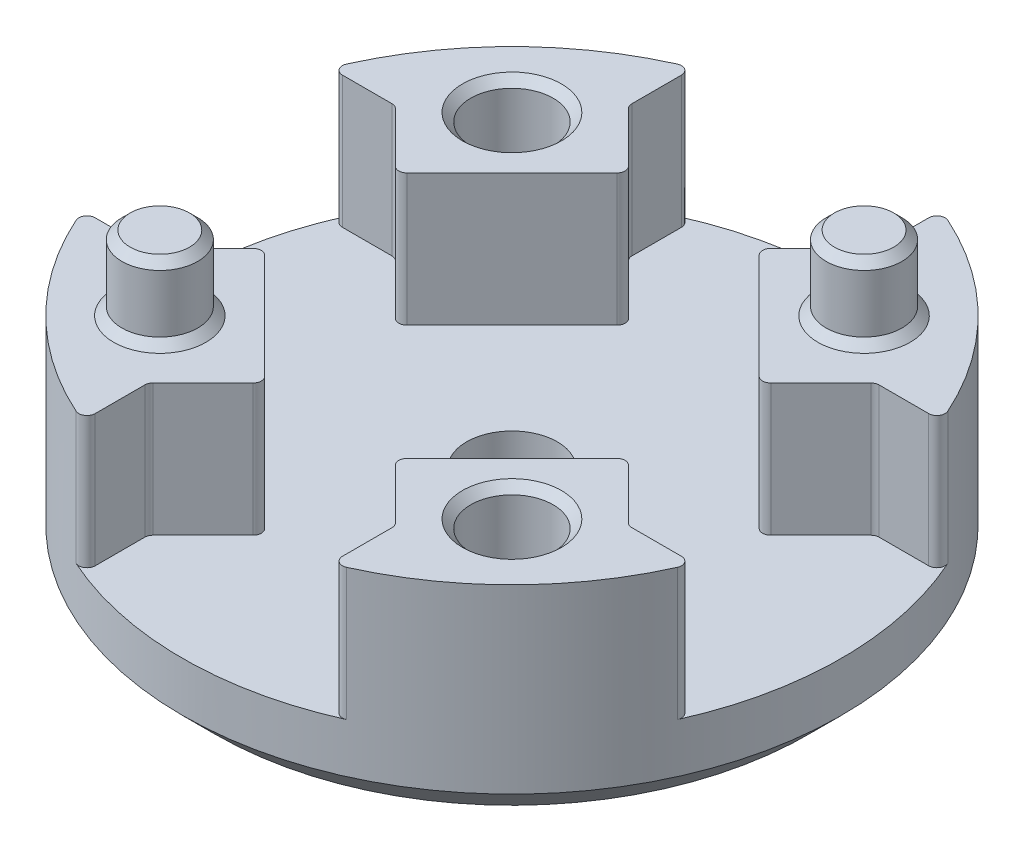
SolidWorks part; units mm, degrees
ref_plane "前视基准面" through (0, 0, 0) normal (0, 0, 1) x (1, 0, 0)
ref_plane "上视基准面" through (0, 0, 0) normal (0, 1, 0) x (1, 0, 0)
ref_plane "右视基准面" through (0, 0, 0) normal (1, 0, 0) x (0, 0, -1)
sketch "草图1" plane through (0, 0, 0) normal (0, 1, 0) x (1, 0, 0)
  circle A0 centre (0, 0) radius 20
  dimension "D1" = 40
extrude "凸台-拉伸1" add sketch "草图1" along normal blind 5
sketch "草图2" plane through (0, 5, 0) normal (0, 1, 0) x (1, 0, 0)
  line L0 (0, -15) -> (7.5, -7.5) construction
  line L1 (0, -15) -> (-7.5, -7.5) construction
  line L2 (7.5, -7.5) -> (0, 0) construction
  line L3 (-7.5, -7.5) -> (0, 0) construction
  line L4 (0, -15) -> (0, 0) construction
  line L5 (7.5, -7.5) -> (-7.5, -7.5) construction
  line L6 (14.5711, -7.5) -> (7.5, -14.5711) construction
  line L7 (14.5711, -7.5) -> (11.0355, -3.9645)
  line L8 (7.5, -14.5711) -> (3.9645, -11.0355)
  line L9 (11.0355, -3.9645) -> (3.9645, -11.0355)
  line L10 (14.5711, -7.5) -> (3.9645, -11.0355) construction
  line L11 (7.5, -14.5711) -> (11.0355, -3.9645) construction
  line L12 (7.5, -14.5711) -> (7.5, -18.5405)
  line L13 (14.5711, -7.5) -> (18.5405, -7.5)
  circle A0 centre (0, 0) radius 20 construction
  arc A1 (7.5, -18.5405) -> (18.5405, -7.5) centre (0, 0) ccw
  point P1 (0, -7.5)
  point P2 (9.2678, -9.2678)
  dimension "D1" = 15
  dimension "D2" = 5
  dimension "D3" = 5
extrude "凸台-拉伸2" add sketch "草图2" along normal blind 8
fillet "圆角1" radius 0.5 6 edges at (18.5405, 9, 7.5) (14.5711, 9, 7.5) (7.5, 9, 18.5405) (7.5, 9, 14.5711) (11.0355, 9, 3.9645) (3.9645, 9, 11.0355)
pattern_circular "阵列(圆周)1" count 4 over 360 about axis through (0, 5, 0) along (0, -1, 0) of "凸台-拉伸2", "圆角1" reverse direction yes
sketch "草图3" plane through (0, 13, 0) normal (0, 1, 0) x (1, 0, 0)
  line L0 (10.682, -10.682) -> (0, 0) construction
  line L1 (10.682, -4.318) -> (4.318, -10.682) construction
  line L2 (0, 0) -> (10.682, -10.682) construction
  circle A0 centre (10.682, -10.682) radius 2.5
  circle A1 centre (-10.682, -10.682) radius 2.5 construction
  circle A2 centre (-10.682, 10.682) radius 2.5
  circle A3 centre (10.682, 10.682) radius 2.5 construction
  circle A5 centre (10.682, 10.682) radius 2.3
  circle A6 centre (-10.682, -10.682) radius 2.3
  dimension "D2" = 5
  dimension "D1" = 4.5
  dimension "D3" = 4
  dimension "D4" = 15.1066
  dimension "D5" = 0.2
  dimension "D6" = 0.2
extrude "切除-拉伸1" cut sketch "草图3" against normal blind 5 contours A2 | A0 region at (10.682, 13, 10.682) region at (-10.682, 13, -10.682)
extrude "凸台-拉伸3" add sketch "草图3<3>" along normal blind 4.5 contours A3 | A1 | A5 | A6 region at (10.682, 13, -10.682) region at (-10.682, 13, 10.682)
sketch "草图3<3>" plane through (0, 13, 0) normal (0, 1, 0) x (1, 0, 0) same geometry as "草图3"
chamfer "倒角1" distance 0.5 angle 45 8 edges at (10.682, 13, 13.182) (10.682, 8, 13.182) (-10.682, 13, -8.182) (-10.682, 8, -8.182) (10.682, 13, -8.382) (10.682, 17.5, -8.382) (-10.682, 13, 12.982) (-10.682, 17.5, 12.982)
sketch "草图4" plane through (0, 0, 0) normal (0, -1, 0) x (1, 0, 0)
  circle A0 centre (0, 0) radius 2.75
  dimension "D1" = 5.5
extrude "切除-拉伸2" cut sketch "草图4" against normal through all
chamfer "倒角2" distance 2 angle 45 1 edges at (0, 0, 20)
